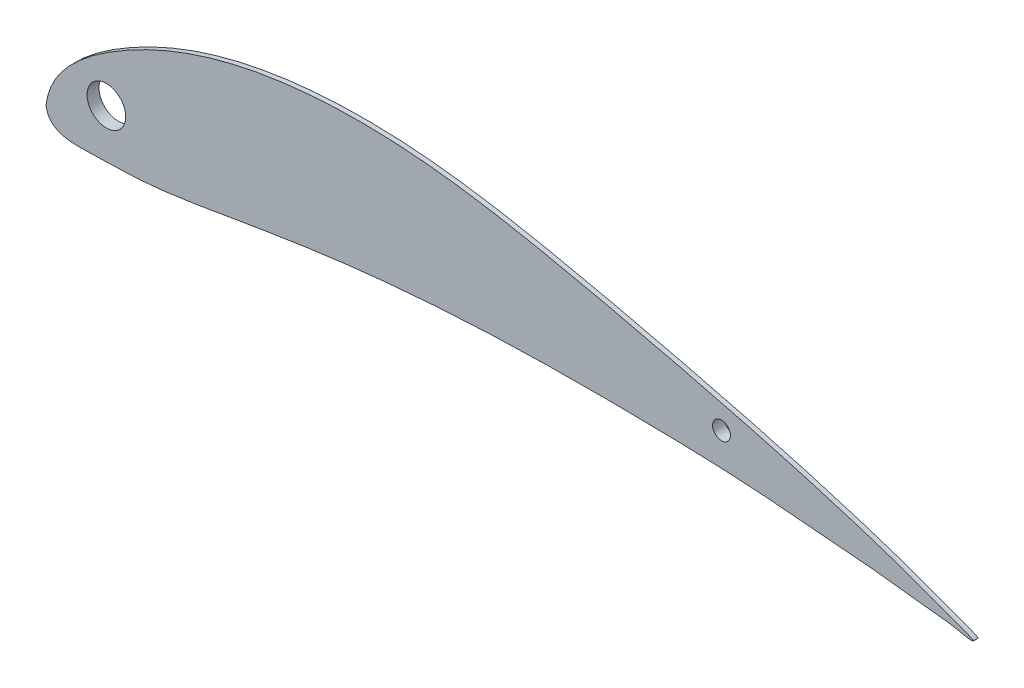
SolidWorks part; units mm, degrees
material "ABS"
ref_plane "Front Plane" through (0, 0, 0) normal (0, 0, 1) x (1, 0, 0)
ref_plane "Top Plane" through (0, 0, 0) normal (0, 1, 0) x (1, 0, 0)
ref_plane "Right Plane" through (0, 0, 0) normal (1, 0, 0) x (0, 0, -1)
sketch "Sketch1" plane through (0, 0, 0) normal (0, 0, 1) x (1, 0, 0)
  spline S0 degree 3 poles (0.0006, 0.0001) (0.8106, 7.3592) (8.6491, 17.8566) (26.2867, 29.9752) (52.1111, 42.0692) (89.5976, 49.2908) (131.4008, 47.8848) (173.2567, 40.0411) (217.9611, 29.613) (256.9521, 19.5289) (290.3598, 8.711) (301.2732, 4.3828) (314.8169, -0.5162) (309.8463, 0.0001) knots 0 0 0 0 0.060864 0.113688 0.188609 0.312909 0.448482 0.557612 0.691544 0.852438 0.929756 0.976058 1 1 1 1
  spline S1 degree 3 poles (309.8463, 0.0001) (303.9568, 1.471) (293.9895, 2.094) (276.264, 4.5144) (260.8463, 5.4274) (235.8588, 7.8703) (205.1014, 8.8381) (157.7186, 9.0307) (110.4973, 6.1815) (66.5062, -0.5867) (36.4547, -6.0985) (15.3166, -6.1891) (1.2307, -6.9241) (0.0006, 0.0001) knots 0 0 0 0 0.057787 0.095275 0.171021 0.205339 0.335319 0.464904 0.658702 0.785512 0.893517 0.943092 1 1 1 1
extrude "Boss-Extrude1" add sketch "Sketch1" along normal blind 1.5875
sketch "Sketch2" plane through (0, 0, 1.5875) normal (0, 0, 1) x (1, 0, 0)
  circle A0 centre (20.32, 10.16) radius 6.5
  circle A1 centre (227.2963, 19.0501) radius 3
  circle A2 centre (20.32, 10.16) radius 5.75
  circle A3 centre (20.32, 10.16) radius 8
  circle A4 centre (227.2963, 19.0501) radius 4.5
  circle A5 centre (227.2963, 19.0501) radius 2.5
  dimension "D2" = 13
  dimension "D3" = 6
  dimension "D6" = 20.32
  dimension "D7" = 1.5
  dimension "D8" = 11.5
  dimension "D9" = 5
  dimension "D10" = 1.5
  dimension "D1" = 82.55
  dimension "D4" = 19.05
  dimension "D5" = 10.16
extrude "Boss-Extrude2" add sketch "Sketch2" against normal blind 4 contours A4 A1 | A3 A0 region at (12.5463, 10.16, 1.5875) region at (222.9236, 19.0501, 1.5875)
extrude "Cut-Extrude1" cut sketch "Sketch2<4>" against normal blind 4 contours A5 | A2 | A0 A2 | A1 A5 region at (14.0038, 10.16, 1.5875) region at (224.3812, 19.0501, 1.5875) region at (20.32, 10.16, 1.5875) region at (227.2963, 19.0501, 1.5875)
sketch "Sketch2<4>" plane through (0, 0, 1.5875) normal (0, 0, 1) x (1, 0, 0) same geometry as "Sketch2"
